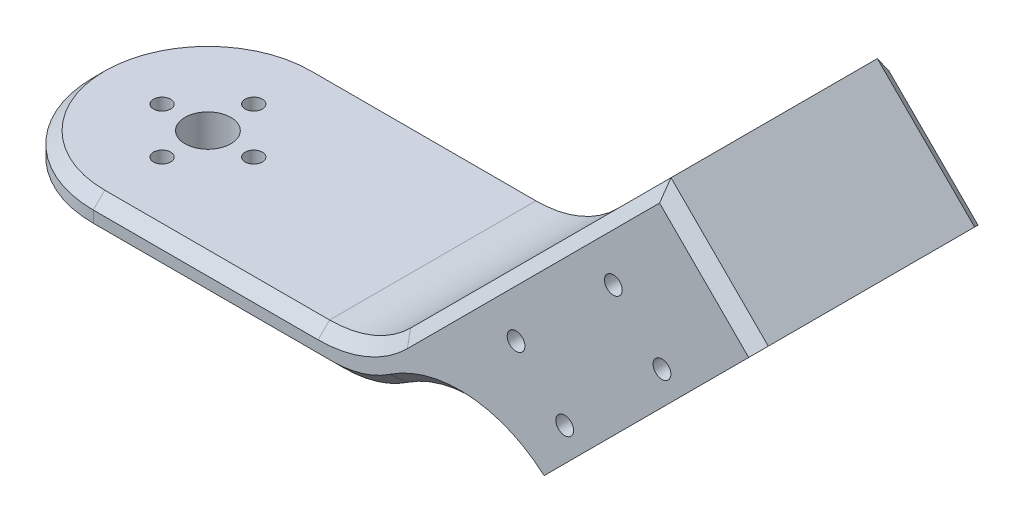
SolidWorks part; units mm, degrees
ref_plane "Front Plane" through (0, 0, 0) normal (0, 0, 1) x (1, 0, 0)
ref_plane "Top Plane" through (0, 0, 0) normal (0, 1, 0) x (1, 0, 0)
ref_plane "Right Plane" through (0, 0, 0) normal (1, 0, 0) x (0, 0, -1)
sketch "Sketch1" plane through (0, 0, 0) normal (0, 0, 1) x (1, 0, 0)
  line L0 (70, 0) -> (123.033, 53.033)
  line L1 (0, 0) -> (70, 0)
  line L2 (0, 0) -> (0, 6)
  line L3 (0, 6) -> (70, 6)
  line L4 (70, 0) -> (70, 6)
  line L9 (70, 0) -> (65.7574, 4.2426)
  line L10 (65.7574, 4.2426) -> (70, 0)
  line L11 (65.7574, 4.2426) -> (118.7904, 57.2756)
  line L12 (70, 0) -> (123.033, 53.033)
  line L13 (118.7904, 57.2756) -> (123.033, 53.033)
  dimension "D1" = 70
  dimension "D2" = 75
  dimension "D3" = 6
  dimension "D4" = 6
  dimension "D5" = 45
  dimension "D6" = 90
extrude "Boss-Extrude1" add sketch "Sketch1" along normal blind 40 contours L1 L3 L2 | L1 L4 L3 | L3 region at (95.2839, 29.4923, 0) region at (68.4645, 3.7071, 0) region at (33.7681, 2.974, 0)
sketch "Sketch2" plane through (35, -35, 0) normal (0.7071, -0.7071, 0) x (0, 0, -1)
  line L0 (0, 49.4975) -> (0, 124.4975) construction
  line L1 (-40, 124.4975) -> (0, 124.4975)
  line L2 (-40, 124.4975) -> (-40, 69.9975)
  line L3 (-40, 69.9975) -> (0, 69.9975)
  line L4 (0, 124.4975) -> (0, 69.9975)
  line L9 (-36, 120.4975) -> (-36, 73.9975)
  line L10 (-36, 73.9975) -> (-4, 73.9975)
  line L11 (-4, 120.4975) -> (-4, 73.9975)
  line L12 (-36, 120.4975) -> (-4, 120.4975)
  line L14 (-34.5, 73.9975) -> (-5.5, 73.9975)
  line L15 (-34.5, 73.9975) -> (-34.5, 120.4975)
  line L16 (-34.5, 120.4975) -> (-5.5, 120.4975)
  line L17 (-5.5, 73.9975) -> (-5.5, 120.4975)
  line L18 (-34.5, 73.9975) -> (-5.5, 120.4975) construction
  line L19 (-34.5, 120.4975) -> (-5.5, 73.9975) construction
  point P11 (-20, 97.2475)
  point P16 (-20, 124.4975)
  line M5 (0, 49.4975) -> (0, 124.4975)
  line M6 (0, 124.4975) -> (-40, 124.4975)
  line M7 (-40, 124.4975) -> (-40, 49.4975)
  dimension "D1" = 54.5
  dimension "D3" = 29
  dimension "D4" = 0
  dimension "D5" = 0
  dimension "D6" = 0
  dimension "D2" = 4
extrude "Boss-Extrude2" add sketch "Sketch2" along normal blind 18 contours L3 L9 L12 L11 L10 M7 M5 M6 | L10 L15 L12 L9 | L17 L10 L11 L12 region at (122.555, 52.555, 20) region at (103.7643, 33.7643, 35.25) region at (103.7643, 33.7643, 4.75)
sketch "Sketch3" plane through (35, -35, 0) normal (0.7071, -0.7071, 0) x (0, 0, -1)
  line L4 (-5.5, 120.4975) -> (-34.5, 120.4975)
  line L12 (-5.5, 120.4975) -> (-34.5, 120.4975)
  line L21 (-34.5, 73.9975) -> (-5.5, 73.9975)
  line L25 (-34.5, 73.9975) -> (-5.5, 73.9975)
  line L28 (-34.5, 120.4975) -> (-34.5, 73.9975)
  line L29 (-34.5, 120.4975) -> (-34.5, 73.9975)
  line L30 (-5.5, 73.9975) -> (-5.5, 120.4975)
  line L31 (-5.5, 73.9975) -> (-5.5, 120.4975)
  dimension "D1" = 0
extrude "Cut-Extrude1" cut sketch "Sketch3" against normal blind 30
sketch "Sketch4" plane through (0, 6, 0) normal (0, 1, 0) x (1, 0, 0)
  line L0 (0, 0) -> (40, -40) construction
  line L1 (0, -40) -> (67.5147, -40) construction
  circle A0 centre (20, -20) radius 4
  circle A1 centre (20, -12) radius 1.5
  circle A2 centre (28, -20) radius 1.5
  circle A3 centre (20, -28) radius 1.5
  circle A4 centre (12, -20) radius 1.5
  point P18 (20, -20)
  dimension "D1" = 8
  dimension "D3" = 3
  dimension "D2" = 8
  dimension "D4" = 4
extrude "Cut-Extrude2" cut sketch "Sketch4" against normal blind 30
sketch "Sketch8" plane through (0, 0, 40) normal (0, 0, 1) x (1, 0, 0)
  circle A0 centre (110.7294, 38.0423) radius 1.05 construction
  circle A1 centre (119.2146, 29.5571) radius 1.05 construction
  circle A2 centre (102.2441, 12.5865) radius 1.05 construction
  circle A3 centre (93.7588, 21.0718) radius 1.05 construction
  circle A4 centre (110.7294, 38.0423) radius 1.05
  circle A5 centre (119.2146, 29.5571) radius 1.05
  circle A6 centre (102.2441, 12.5865) radius 1.05
  circle A7 centre (93.7588, 21.0718) radius 1.05
  circle A8 centre (93.7588, 21.0718) radius 1.55
  circle A9 centre (102.2441, 12.5865) radius 1.55
  circle A10 centre (119.2146, 29.5571) radius 1.55
  circle A11 centre (110.7294, 38.0423) radius 1.55
  dimension "D1" = 0.5
extrude "Cut-Extrude3" cut sketch "Sketch8" against normal through all both and the other way through all contours A8 A7 | A7 | A9 A6 | A6 | A11 A4 | A4 | A10 A5 | A5 region at (110.7294, 38.0423, 40) region at (119.2146, 29.5571, 40) region at (102.2441, 12.5865, 40) region at (93.7588, 21.0718, 40) region at (92.2526, 21.0718, 40) region at (100.7379, 12.5865, 40) region at (117.7085, 29.5571, 40) region at (109.2232, 38.0423, 40)
fillet "Fillet1" radius 20 2 edges at (67.5147, 6, 20) (70, 0, 20)
fillet "Fillet2" radius 20 1 edges at (84.4957, 14.4957, 20)
fillet "Fillet3" radius 20 2 edges at (0, 3, 0) (0, 3, 40)
chamfer "Chamfer1" distance 2 angle 45 18 edges at (127.2756, 48.7904, 0) (127.2756, 48.7904, 40) (85.3136, 6.7301, 0) (67.5356, 0.8655, 0) (40.8579, 0, 0) (5.8579, 0, 5.8579) (85.3136, 6.7301, 40) (5.8579, 0, 34.1421) (67.5356, 0.8655, 40) (40.8579, 0, 40) (96.0815, 34.5668, 0) (66.8841, 7.5224, 0) (39.6152, 6, 0) (5.8579, 6, 5.8579) (96.0815, 34.5668, 40) (5.8579, 6, 34.1421) (66.8841, 7.5224, 40) (39.6152, 6, 40)
